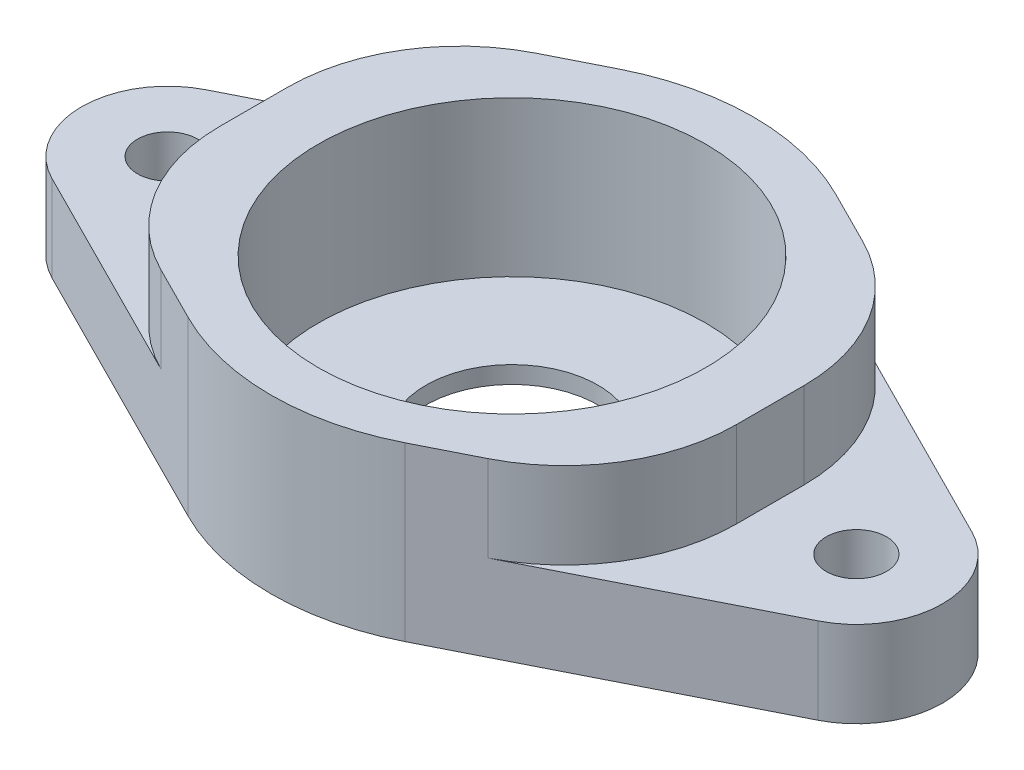
SolidWorks part; units mm, degrees
ref_plane "Front Plane" through (0, 0, 0) normal (0, 0, 1) x (1, 0, 0)
ref_plane "Top Plane" through (0, 0, 0) normal (0, 1, 0) x (1, 0, 0)
ref_plane "Right Plane" through (0, 0, 0) normal (1, 0, 0) x (0, 0, -1)
sketch "Sketch2" plane through (0, 0, 0) normal (0, 1, 0) x (1, 0, 0)
  line L0 (-22.25, 4.4651) -> (-6.3, 12.5024)
  line L1 (6.3, 12.5024) -> (22.25, 4.4651)
  line L2 (-22.25, -4.4651) -> (-6.3, -12.5024)
  line L3 (6.3, -12.5024) -> (22.25, -4.4651)
  arc A0 (6.3, 12.5024) -> (-6.3, 12.5024) centre (0, 0) ccw
  arc A1 (-22.25, 4.4651) -> (-22.25, -4.4651) centre (-20, 0) ccw
  arc A2 (22.25, -4.4651) -> (22.25, 4.4651) centre (20, 0) ccw
  circle A4 centre (-20, 0) radius 1.75
  circle A5 centre (20, 0) radius 1.75
  arc A6 (-6.3, -12.5024) -> (6.3, -12.5024) centre (0, 0) ccw
  dimension "D1" = 28
  dimension "D2" = 10
  dimension "D3" = 10
  dimension "D4" = 3.5
  dimension "D5" = 3.5
  dimension "D6" = 20
  dimension "D7" = 20
extrude "Boss-Extrude1" add sketch "Sketch2" along normal blind 10
sketch "Sketch3" plane through (0, 10, 0) normal (0, 1, 0) x (1, 0, 0)
  circle A0 centre (0, 0) radius 11.25
extrude "Cut-Extrude1" cut sketch "Sketch3" against normal blind 9
sketch "Sketch4" plane through (0, 0, 0) normal (0, 0, 1) x (1, 0, 0)
  line L0 (-22.25, 10) -> (-6.3, 10) construction
  line L1 (-15, 10) -> (-25, 10)
  line L2 (-15, 10) -> (-15, 5)
  line L3 (-15, 5) -> (-25, 5)
  line L4 (-25, 10) -> (-25, 5)
  line L5 (-25, 10) -> (-25, 0) construction
  line L6 (6.3, 10) -> (22.25, 10) construction
  line L7 (15, 10) -> (25, 10)
  line L8 (15, 10) -> (15, 5)
  line L9 (15, 5) -> (25, 5)
  line L10 (25, 10) -> (25, 5)
  line L11 (25, 0) -> (25, 10) construction
  line L12 (-22.25, 0) -> (-6.3, 0) construction
  line L13 (18.25, 0) -> (21.75, 0) construction
  dimension "D1" = 10
  dimension "D2" = 10
  dimension "D3" = 5
  dimension "D4" = 5
extrude "Cut-Extrude2" cut sketch "Sketch4" against normal through all both and the other way through all
fillet "Fillet1" radius 10 4 edges at (15, 7.5, 8.1184) (15, 7.5, -8.1184) (-15, 7.5, -8.1184) (-15, 7.5, 8.1184)
sketch "Sketch5" plane through (0, 1, 0) normal (0, 1, 0) x (1, 0, 0)
  circle A0 centre (0, 0) radius 5
  dimension "D1" = 10
extrude "Cut-Extrude3" cut sketch "Sketch5" against normal through all both and the other way through all
